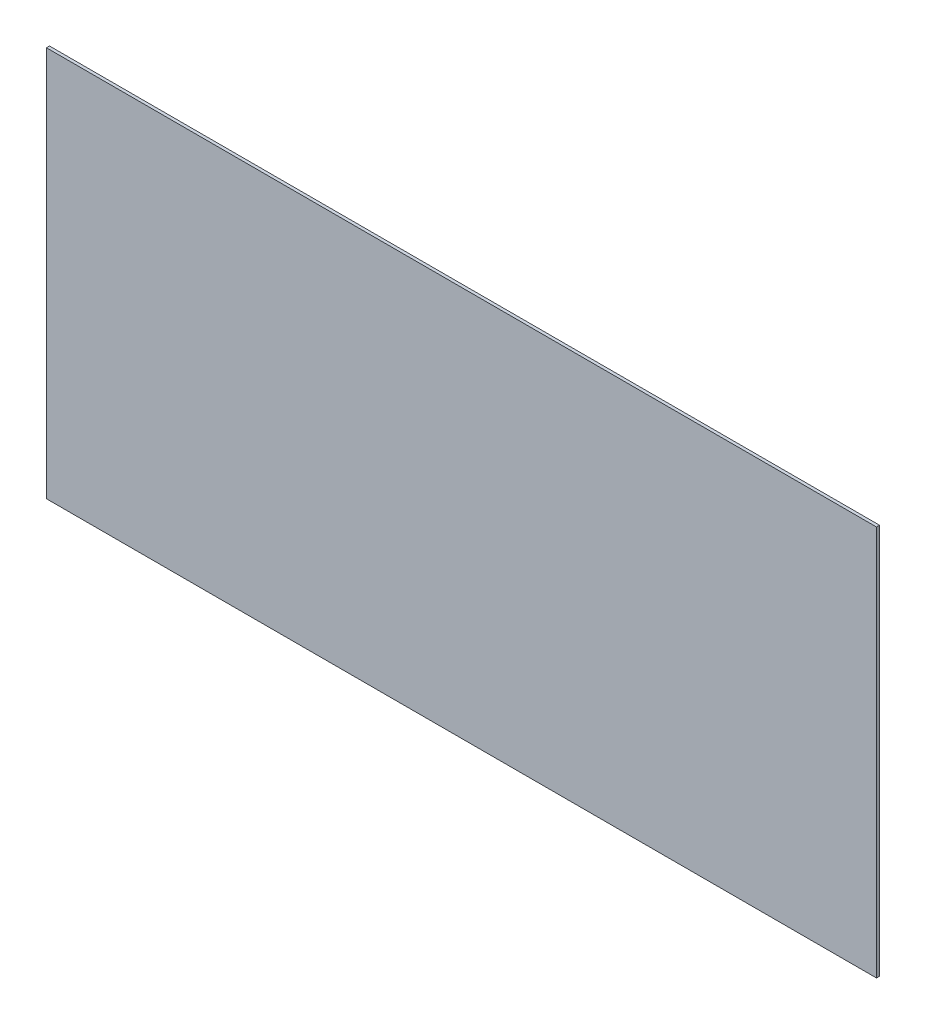
SolidWorks part; units mm, degrees
ref_plane "Front Plane" through (0, 0, 0) normal (0, 0, 1) x (1, 0, 0)
ref_plane "Top Plane" through (0, 0, 0) normal (0, 1, 0) x (1, 0, 0)
ref_plane "Right Plane" through (0, 0, 0) normal (1, 0, 0) x (0, 0, -1)
sketch "Sketch1" plane through (0, 0, 0) normal (0, 0, 1) x (1, 0, 0)
  line L0 (-431.8, 0) -> (431.8, 0) construction
  line L1 (-431.8, 203.2) -> (431.8, 203.2)
  line L2 (-431.8, 203.2) -> (-431.8, -203.2)
  line L3 (-431.8, -203.2) -> (431.8, -203.2)
  line L4 (431.8, 203.2) -> (431.8, -203.2)
  line L5 (0, 203.2) -> (0, -203.2) construction
  point P8 (0, 0)
  dimension "D1" = 863.6
  dimension "D2" = 406.4
extrude "Boss-Extrude1" add sketch "Sketch1" along normal blind 3.175
